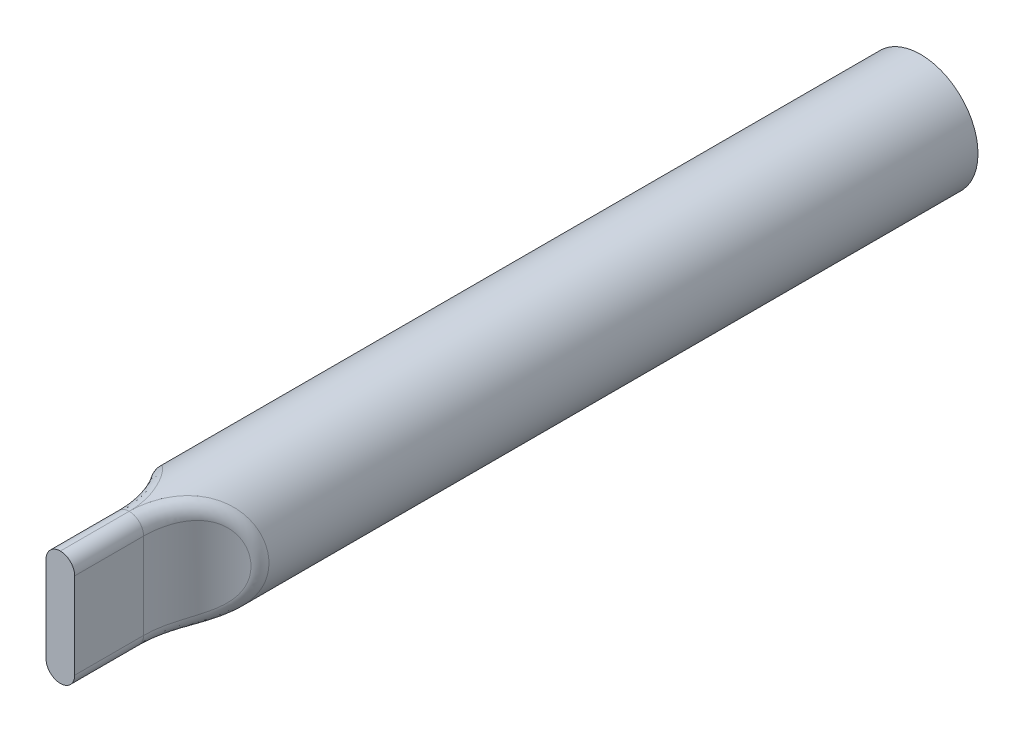
SolidWorks part; units mm, degrees
ref_plane "Front Plane" through (0, 0, 0) normal (0, 0, 1) x (1, 0, 0)
ref_plane "Top Plane" through (0, 0, 0) normal (0, 1, 0) x (1, 0, 0)
ref_plane "Right Plane" through (0, 0, 0) normal (1, 0, 0) x (0, 0, -1)
sketch "Sketch1" plane through (0, 0, 0) normal (0, 0, 1) x (1, 0, 0)
  circle A0 centre (0, 0) radius 2
  dimension "D1" = 4
extrude "Boss-Extrude1" add sketch "Sketch1" along normal blind 30
sketch "Sketch2" plane through (0, 0, 0) normal (0, 1, 0) x (1, 0, 0)
  line L0 (0, -30) -> (0, -25.1492) construction
  line L1 (-2, -30) -> (2, -30) construction
  line L2 (-0.5, -30) -> (-0.5, -27.5981)
  line L3 (-2, 0) -> (-2, -30) construction
  line L4 (-2, -25) -> (-2, -30)
  line L5 (-2, -30) -> (-0.5, -30)
  line L6 (2, -30) -> (0.5, -30)
  line L7 (2, -25) -> (2, -30)
  line L8 (0.5, -30) -> (0.5, -27.5981)
  arc A0 (-0.5, -27.5981) -> (-2, -25) centre (-3.5, -27.5981) ccw
  arc A1 (0.5, -27.5981) -> (2, -25) centre (3.5, -27.5981) cw
  dimension "D2" = 3
  dimension "D1" = 1
  dimension "D3" = 5
extrude "Cut-Extrude1" cut sketch "Sketch2" against normal through all both and the other way through all
fillet "Fillet1" radius 0.5 6 edges at (0.5, -1.9365, 28.799) (1.9982, -0.0842, 25.001) (-0.5, -1.9365, 28.799) (-0.5, 1.9365, 28.799) (0.5, 1.9365, 28.799) (-1.9982, 0.0842, 25.001)
shell "Shell1" thickness 0.25 removed face at (2, 0, 0)
sketch "Sketch3" plane through (0, 0, 0) normal (0, 1, 0) x (1, 0, 0)
  line L0 (0, 0) -> (0, -9) construction
  line L1 (0, -9) -> (0, -14) construction
  line L2 (0, -14) -> (0, -19) construction
  circle A0 centre (0, -19) radius 1
  circle A1 centre (0, -14) radius 1
  circle A2 centre (0, -9) radius 1
  dimension "D1" = 2
  dimension "D2" = 5
  dimension "D3" = 9
extrude "Cut-Extrude2" cut sketch "Sketch3" against normal blind 30
